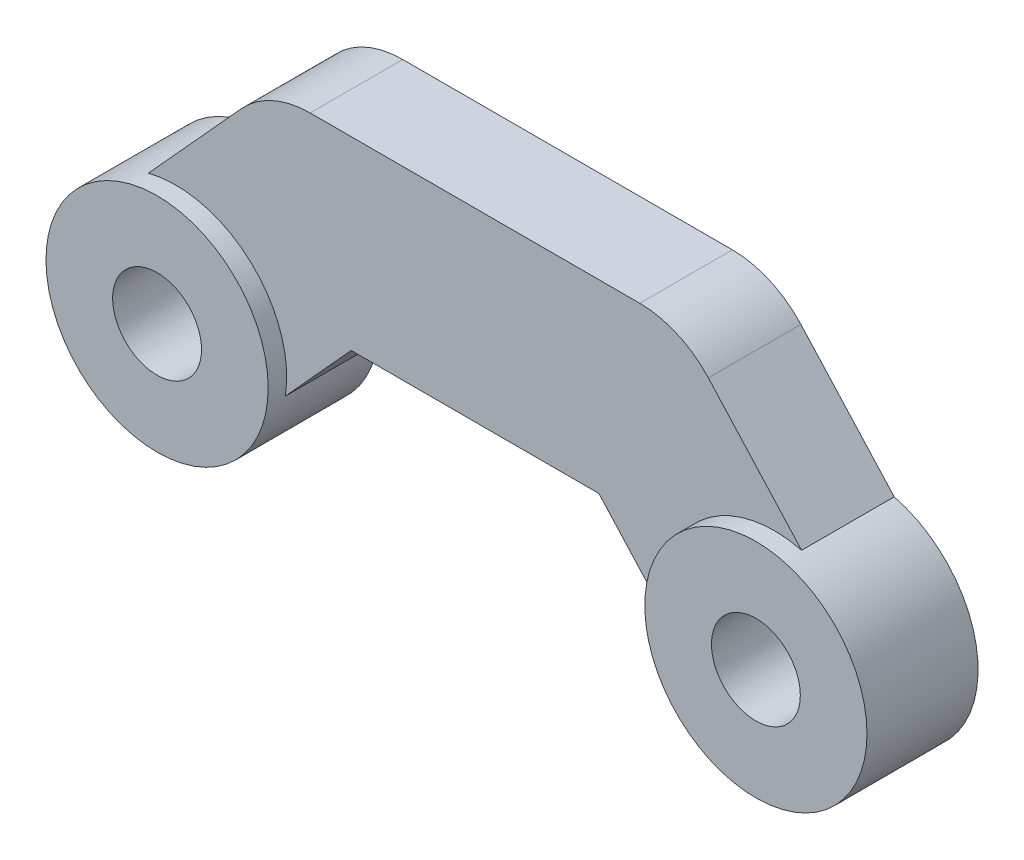
SolidWorks part; units mm, degrees
ref_plane "Front Plane" through (0, 0, 0) normal (0, 0, 1) x (1, 0, 0)
ref_plane "Top Plane" through (0, 0, 0) normal (0, 1, 0) x (1, 0, 0)
ref_plane "Right Plane" through (0, 0, 0) normal (1, 0, 0) x (0, 0, -1)
sketch "Sketch1" plane through (0, 0, 0) normal (0, 0, 1) x (1, 0, 0)
  line L0 (-8.085, 2.5) -> (8.085, 2.5)
  line L1 (-8.085, -2.5) -> (8.085, -2.5)
  line L2 (-8.085, 0) -> (8.085, 0) construction
  line L3 (-8.085, 0) -> (-4.4501, 4) construction
  line L4 (-4.4501, 4) -> (4.4501, 4) construction
  line L5 (4.4501, 4) -> (8.085, 0) construction
  line L6 (-8.085, 0) -> (-4.4501, 4) construction
  line L7 (-9.9352, 1.6813) -> (-6.3003, 5.6813)
  line L8 (-6.2348, -1.6813) -> (-2.5999, 2.3187)
  line L9 (8.085, 0) -> (4.4501, 4) construction
  line L10 (6.2348, -1.6813) -> (2.5999, 2.3187)
  line L11 (9.9352, 1.6813) -> (6.3003, 5.6813)
  line L12 (4.4501, 4) -> (-4.4501, 4) construction
  line L13 (4.4501, 1.5) -> (-4.4501, 1.5)
  line L14 (4.4501, 6.5) -> (-4.4501, 6.5)
  circle A0 centre (-8.085, 0) radius 1.2
  circle A1 centre (-8.085, 0) radius 2.5
  circle A2 centre (8.085, 0) radius 1.2
  circle A3 centre (8.085, 0) radius 2.5
  arc A4 (-9.9352, 1.6813) -> (-6.2348, -1.6813) centre (-8.085, 0) ccw
  arc A5 (-2.5999, 2.3187) -> (-6.3003, 5.6813) centre (-4.4501, 4) ccw
  arc A6 (6.2348, -1.6813) -> (9.9352, 1.6813) centre (8.085, 0) ccw
  arc A7 (6.3003, 5.6813) -> (2.5999, 2.3187) centre (4.4501, 4) ccw
  arc A8 (4.4501, 1.5) -> (4.4501, 6.5) centre (4.4501, 4) ccw
  arc A9 (-4.4501, 6.5) -> (-4.4501, 1.5) centre (-4.4501, 4) ccw
  point P10 (0, 0)
  point P11 (-6.2676, 2)
  point P19 (6.2676, 2)
  point P24 (0, 4)
  dimension "D1" = 2.4
  dimension "D2" = 5
  dimension "D3" = 5
  dimension "D5" = 2.4
  dimension "D4" = 16.17
  dimension "D6" = 4
extrude "Boss-Extrude1" add sketch "Sketch1" along normal mid plane 2.5 contours A7 L14 A5 L8 L0 L10 | A5 A9 L0 L8 | L0 A8 A7 L10 | A8 L0 A3 L11 | A3 L0 L10 | A3 A2 | A9 L7 A1 L0 | A1 L8 L0 | A1 A0 | L0 A9 L13 L8 A5 | L13 A8 L0 A7 L10 | A7 L0 A5 L8 L13 L10 region at (-7.6724, 3.2936, 0) region at (-5.2202, 0.9416, 0) region at (-6.3672, 1.7178, 0) region at (-4.4501, 4.3167, 0) region at (-4.3937, 2.0691, 0) region at (0, 4.6645, 0) region at (0, 1.9739, 0) region at (4.4501, 4.3167, 0) region at (4.3937, 2.0691, 0) region at (7.102, -2.2215, 0) region at (7.6724, 3.2936, 0) region at (5.2202, 0.9416, 0)
sketch "Sketch2" plane through (0, 0, 1.25) normal (0, 0, 1) x (1, 0, 0)
  circle A0 centre (8.085, 0) radius 3
  circle A1 centre (-8.085, 0) radius 3
  circle A2 centre (-8.085, 0) radius 1.2 construction
  circle A3 centre (8.085, 0) radius 1.2 construction
  circle A4 centre (-8.085, 0) radius 1.2
  circle A5 centre (8.085, 0) radius 1.2
  dimension "D1" = 6
extrude "Boss-Extrude2" add sketch "Sketch2" against normal up to surface (2.5 mm away) and the other way blind 0.5 up to face at (0, 2.4053, -1.25)
